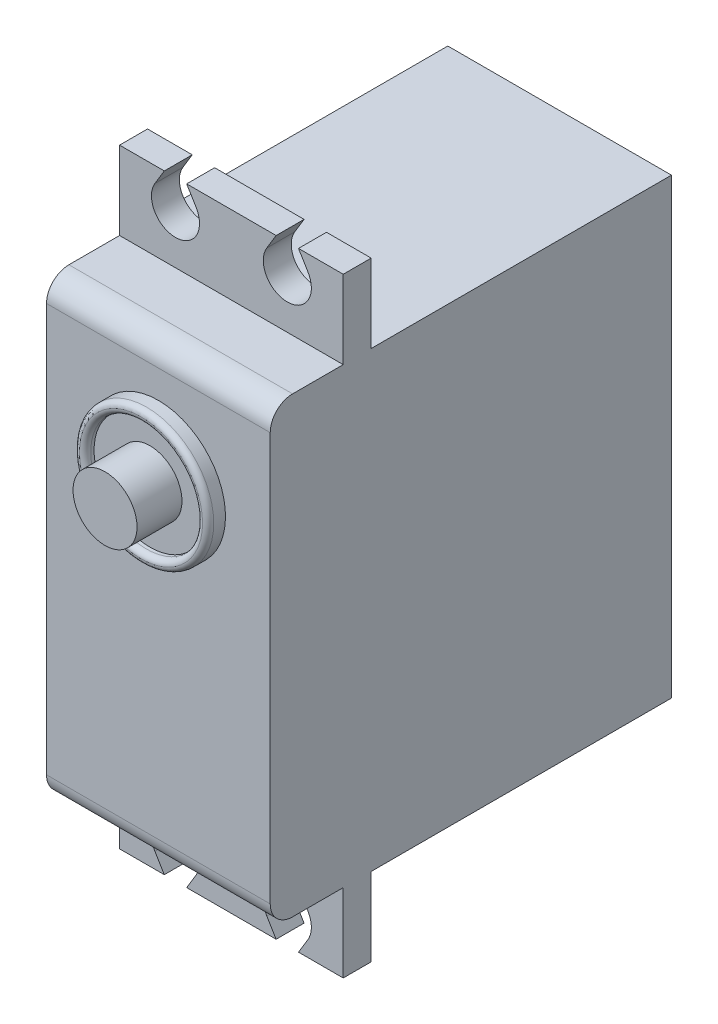
SolidWorks part; units mm, degrees
ref_plane "Front Plane" through (0, 0, 0) normal (0, 0, 1) x (1, 0, 0)
ref_plane "Top Plane" through (0, 0, 0) normal (0, 1, 0) x (1, 0, 0)
ref_plane "Right Plane" through (0, 0, 0) normal (1, 0, 0) x (0, 0, -1)
sketch "Sketch1" plane through (0, 0, 0) normal (1, 0, 0) x (0, 0, -1)
  line L0 (35.88, -20.25) -> (35.88, 20.25)
  line L1 (35.88, 20.25) -> (9.03, 20.25)
  line L2 (9.03, 20.25) -> (9.03, 27.25)
  line L3 (9.03, 27.25) -> (6.53, 27.25)
  line L4 (6.53, 27.25) -> (6.53, 20.25)
  line L5 (0, 18.25) -> (0, -18.25)
  line L6 (35.88, 0) -> (0, 0) construction
  line L7 (6.53, -27.25) -> (6.53, -20.25)
  line L8 (9.03, -27.25) -> (6.53, -27.25)
  line L9 (9.03, -20.25) -> (9.03, -27.25)
  line L10 (35.88, -20.25) -> (9.03, -20.25)
  line L11 (6.53, 20.25) -> (2, 20.25)
  line L12 (6.53, -20.25) -> (2, -20.25)
  arc A2 (2, 20.25) -> (0, 18.25) centre (2, 18.25) ccw
  arc A3 (2, -20.25) -> (0, -18.25) centre (2, -18.25) cw
  dimension "D6" = 2
  dimension "D1" = 7
  dimension "D2" = 2.5
  dimension "D3" = 26.85
  dimension "D4" = 35.88
  dimension "D5" = 40.5
extrude "Boss-Extrude1" add sketch "Sketch1" along normal mid plane 20
sketch "Sketch3" plane through (0, 0, -6.53) normal (0, 0, 1) x (1, 0, 0)
  line L0 (0, 27.25) -> (0, 20.25) construction
  line L1 (10, 27.25) -> (-10, 27.25) construction
  line L2 (10, 20.25) -> (-10, 20.25) construction
  line L3 (-5, 24.75) -> (-5, 27.25) construction
  line L4 (-6.8393, 25.8633) -> (-6, 27.25)
  line L5 (-3.1607, 25.8633) -> (-4, 27.25)
  line L6 (3.1607, 25.8633) -> (4, 27.25)
  line L7 (6.8393, 25.8633) -> (6, 27.25)
  line L8 (5, 24.75) -> (-5, 24.75) construction
  circle A0 centre (-5, 24.75) radius 2.15
  circle A1 centre (5, 24.75) radius 2.15
  line M11 (10, 27.25) -> (-10, 27.25)
  dimension "D2" = 4.3
  dimension "D1" = 2
  dimension "D3" = 10
  dimension "D4" = 24.75
extrude "Cut-Extrude2" cut sketch "Sketch3" against normal up to surface (2.5 mm away) contours A0 | A0 L5 L4 M11 | A1 | L6 A1 L7 M11 region at (5, 26.9242, -6.53) region at (-5, 26.9242, -6.53) region at (-5, 24.75, -6.53) region at (5, 24.75, -6.53) up to face at (0, 23.75, -9.03)
sketch "Sketch2" plane through (0, 0, 0) normal (0, 0, 1) x (1, 0, 0)
  line L0 (-10, 9.75) -> (10, 9.75) construction
  line L1 (-10, 18.25) -> (-10, -18.25) construction
  line L2 (10, 18.25) -> (10, -18.25) construction
  circle A0 centre (0, 9.75) radius 6
  circle A1 centre (0, 9.75) radius 5
  circle A2 centre (0, 9.75) radius 2.86
  arc A3 (-6.8393, 25.8633) -> (-3.1607, 25.8633) centre (-5, 24.75) ccw construction
  dimension "D2" = 12
  dimension "D3" = 1
  dimension "D4" = 5.72
  dimension "D1" = 15
extrude "Boss-Extrude2" add sketch "Sketch2" along normal blind 1.55 contours A0
extrude "Cut-Extrude1" cut sketch "Sketch2<3>" against normal blind 0.8 from surface contours L0 A1 A2 | L0 A2 | A2 L0 | A1 L0 A2 | A1 region at (0, 12.7218, 0) region at (0, 8.5362, 0) region at (0, 10.9638, 0) region at (3.93, 9.6382, 0) starting at face at (6, 9.75, 1.55)
sketch "Sketch2<3>" plane through (0, 0, 0) normal (0, 0, 1) x (1, 0, 0) same geometry as "Sketch2"
extrude "Boss-Extrude3" add sketch "Sketch2<4>" along normal blind 4.77 contours A2
sketch "Sketch2<4>" plane through (0, 0, 0) normal (0, 0, 1) x (1, 0, 0) same geometry as "Sketch2"
mirror "Mirror1" about plane through (0, 0, 0) normal (0, 1, 0) of "Cut-Extrude2"
fillet "Fillet1" radius 0.5 2 edges at (5, 9.75, 1.55) (6, 9.75, 1.55)
